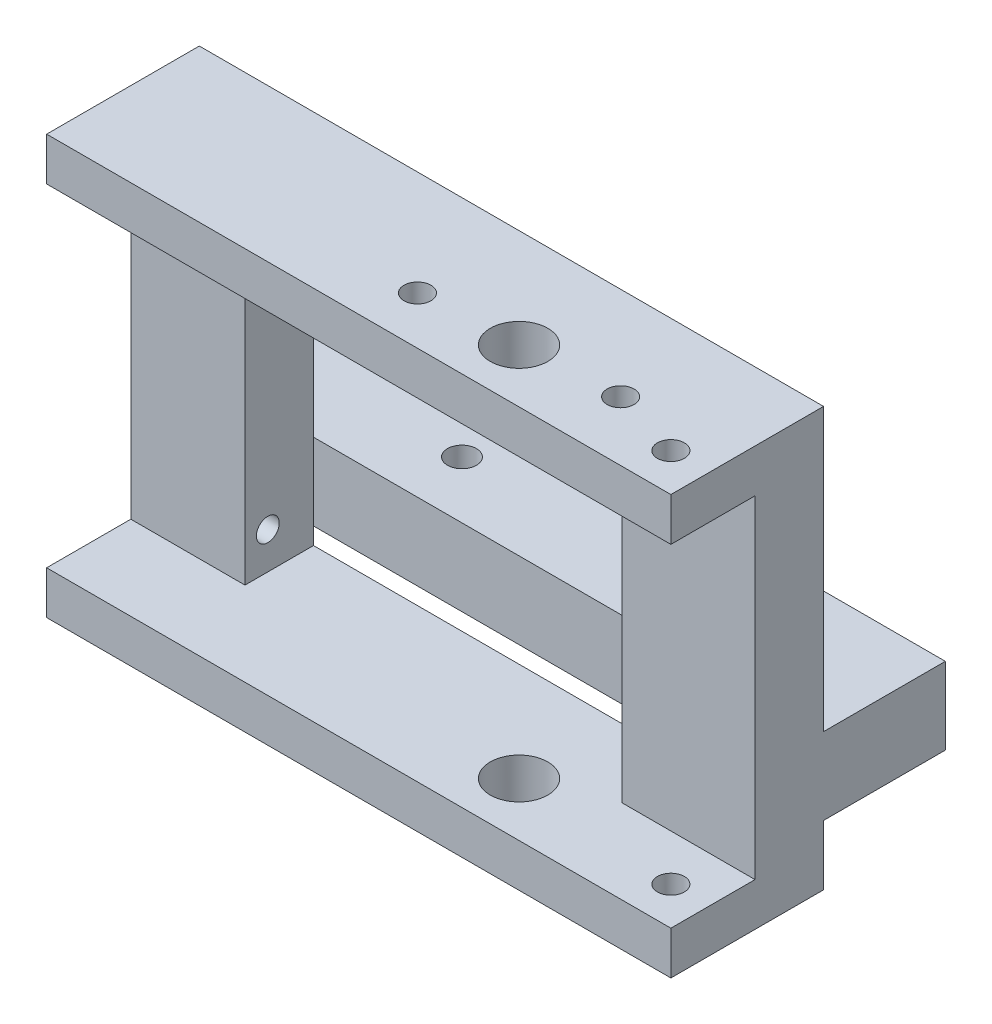
SolidWorks part; units mm, degrees
ref_plane "Front Plane" through (0, 0, 0) normal (0, 0, 1) x (1, 0, 0)
ref_plane "Top Plane" through (0, 0, 0) normal (0, 1, 0) x (1, 0, 0)
ref_plane "Right Plane" through (0, 0, 0) normal (1, 0, 0) x (0, 0, -1)
sketch "Sketch1" plane through (0, 0, 0) normal (0, 0, 1) x (1, 0, 0)
  line L1 (57.15, -34.925) -> (-57.15, -34.925)
  line L2 (57.15, -34.925) -> (57.15, 34.925)
  line L3 (57.15, 34.925) -> (-57.15, 34.925)
  line L4 (-57.15, -34.925) -> (-57.15, 34.925)
  line L5 (57.15, -34.925) -> (-57.15, 34.925) construction
  line L6 (57.15, 34.925) -> (-57.15, -34.925) construction
  point P0 (0, 0)
  dimension "D1" = 69.85
  dimension "D2" = 114.3
extrude "Boss-Extrude1" add sketch "Sketch1" along normal blind 57.15
sketch "Sketch2" plane through (0, 0, 57.15) normal (0, 0, 1) x (1, 0, 0)
  line L0 (-57.15, 34.925) -> (-57.15, -34.925) construction
  line L1 (57.15, -27.725) -> (-57.15, -27.725)
  line L2 (57.15, -27.725) -> (57.15, 27.725)
  line L3 (57.15, 27.725) -> (-57.15, 27.725)
  line L4 (-57.15, -27.725) -> (-57.15, 27.725)
  line L5 (57.15, -27.725) -> (-57.15, 27.725) construction
  line L6 (57.15, 27.725) -> (-57.15, -27.725) construction
  line L7 (57.15, 34.925) -> (-57.15, 34.925) construction
  point P0 (0, 0)
  dimension "D1" = 7.2
extrude "Cut-Extrude2" cut sketch "Sketch2" against normal blind 25.4
sketch "Sketch3" plane through (0, 0, 0) normal (0, 0, -1) x (-1, 0, 0)
  line L0 (-57.15, -34.925) -> (-57.15, 34.925) construction
  line L1 (57.15, 34.925) -> (-57.15, 34.925)
  line L2 (57.15, 34.925) -> (57.15, -12.065)
  line L3 (57.15, -12.065) -> (-57.15, -12.065)
  line L4 (-57.15, 34.925) -> (-57.15, -12.065)
  dimension "D1" = 46.99
extrude "Cut-Extrude3" cut sketch "Sketch3" against normal blind 20.32
sketch "Sketch5" plane through (0, -34.925, 0) normal (0, -1, 0) x (1, 0, 0)
  line L0 (-3.81, 10.79) -> (46.99, 10.79) construction
  line L1 (57.15, 20.32) -> (-57.15, 20.32) construction
  line L2 (57.15, 57.15) -> (57.15, 0) construction
  circle A0 centre (-3.81, 10.79) radius 2.415
  circle A1 centre (46.99, 10.79) radius 2.415
  dimension "D3" = 4.83
  dimension "D4" = 10.16
  dimension "D1" = 9.53
  dimension "D2" = 50.8
sketch "Sketch7" plane through (0, -34.925, 0) normal (0, -1, 0) x (1, 0, 0)
  line L0 (57.15, 57.15) -> (57.15, 0) construction
  line L2 (-57.15, 31.75) -> (57.15, 31.75) construction
  circle A0 centre (31.75, 36.83) radius 4.8
  dimension "D1" = 9.6
  dimension "D2" = 25.4
  dimension "D3" = 5.08
extrude "Cut-Extrude6" cut sketch "Sketch7" against normal up to surface (69.85 mm away) up to face at (0, 34.925, 38.735)
sketch "Sketch8" plane through (0, 34.925, 0) normal (0, 1, 0) x (1, 0, 0)
  line L0 (15.7798, -37.8068) -> (47.7202, -35.8532) construction
  line L1 (57.15, -31.75) -> (-57.15, -31.75) construction
  circle A0 centre (31.75, -36.83) radius 16 construction
  circle A1 centre (15.7798, -37.8068) radius 2.25
  circle A2 centre (47.7202, -35.8532) radius 2.25
  dimension "D1" = 32
  dimension "D2" = 4.5
  dimension "D3" = 3.5
sketch "Sketch9" plane through (0, 0, 31.75) normal (0, 0, 1) x (1, 0, 0)
  line L0 (57.15, 34.925) -> (-57.15, 34.925) construction
  line L5 (57.15, 27.725) -> (-57.15, 27.725) construction
  line L6 (-19.05, 27.725) -> (43.815, 27.725)
  line L7 (-19.05, 27.725) -> (-19.05, -27.725)
  line L8 (-19.05, -27.725) -> (43.815, -27.725)
  line L9 (43.815, 27.725) -> (43.815, -27.725)
  line L10 (-57.15, -27.725) -> (57.15, -27.725) construction
  line L11 (-57.15, 27.725) -> (-57.15, -27.725) construction
  line L12 (57.15, -27.725) -> (57.15, 27.725) construction
  line L13 (-57.15, -34.925) -> (-38.1, -34.925)
  line L14 (-57.15, -34.925) -> (-57.15, 34.925)
  line L15 (-57.15, 34.925) -> (-38.1, 34.925)
  line L16 (-38.1, -34.925) -> (-38.1, 34.925)
  line L17 (-57.15, -34.925) -> (-38.1, 34.925) construction
  line L18 (-57.15, 34.925) -> (-38.1, -34.925) construction
  line L19 (-57.15, -34.925) -> (57.15, -34.925) construction
  point P5 (-47.625, 0)
  dimension "D1" = 13.335
  dimension "25in" = 38.1
  dimension "D2" = 19.05
extrude "Cut-Extrude7" cut sketch "Sketch9" against normal through all both and the other way through all
extrude "Cut-Extrude8" cut sketch "Sketch8" against normal up to next
sketch "Sketch10" [suppressed] plane through (0, 0, 29.21) normal (0, 0, 1) x (1, 0, 0)
  line L1 (-30.607, -1.778) -> (-30.607, -6.604) construction
  circle A0 centre (-33.2489, -4.191) radius 2.286
  point P5 (-30.607, -4.191)
  dimension "D1" = 4.572
sketch "Sketch11" [suppressed] plane through (0, 0, 20.32) normal (0, 0, -1) x (-1, 0, 0)
  circle A0 centre (33.2489, -4.191) radius 2.286
  dimension "D1" = 4.572
extrude "Cut-Extrude9" [suppressed] cut sketch "Sketch11" against normal blind 3.81
sketch "Sketch12" plane through (-19.05, 0, 0) normal (1, 0, 0) x (0, 0, -1)
  line L0 (-31.75, -27.725) -> (-31.75, 27.725) construction
  line L1 (-27.94, -21.59) -> (-27.94, 21.59) construction
  line L2 (-20.32, 27.725) -> (-20.32, -12.065) construction
  circle A0 centre (-27.94, -21.59) radius 1.905
  circle A1 centre (-27.94, 21.59) radius 1.905
  point P0 (-31.75, 0)
  point P8 (-27.94, 0)
  dimension "D1" = 3.81
  dimension "D2" = 7.62
  dimension "D3" = 43.18
extrude "Cut-Extrude10" cut sketch "Sketch12" against normal up to surface (19.05 mm away) up to face at (-38.1, -2.413, 33.274)
sketch "Sketch13" plane through (0, 34.925, 0) normal (0, 1, 0) x (1, 0, 0)
  line L0 (-38.1, -45.7884) -> (57.15, -45.7884)
  line L2 (57.15, -57.15) -> (-38.1, -57.15) construction
  line L3 (47.7202, -35.8532) -> (15.7798, -37.8068) construction
  line L4 (-38.1, -45.7884) -> (-38.1, -57.15)
  line L5 (-38.1, -57.15) -> (57.15, -57.15)
  line L6 (-38.1, -20.32) -> (-38.1, -57.15) construction
  line L7 (57.15, -57.15) -> (57.15, -20.32) construction
  line L8 (57.15, -45.7884) -> (57.15, -57.15)
extrude "Cut-Extrude12" cut sketch "Sketch13" against normal through all
sketch "Sketch14" plane through (43.815, 0, 0) normal (-1, 0, 0) x (0, 0, 1)
  line L0 (0, -27.725) -> (31.75, -27.725) construction
  line L1 (20.32, -12.065) -> (0, -12.065)
  line L2 (20.32, -12.065) -> (20.32, -27.725)
  line L3 (20.32, -27.725) -> (0, -27.725)
  line L4 (0, -12.065) -> (0, -27.725)
extrude "Boss-Extrude2" add sketch "Sketch14" along normal up to next
sketch "Sketch16" plane through (0, 0, 31.75) normal (0, 0, 1) x (1, 0, 0)
  line L0 (43.815, -27.725) -> (43.815, 27.725) construction
  line L1 (57.15, -6.35) -> (43.815, -6.35)
  line L2 (57.15, -6.35) -> (57.15, 6.35)
  line L3 (57.15, 6.35) -> (43.815, 6.35)
  line L4 (43.815, -6.35) -> (43.815, 6.35)
  line L5 (57.15, -6.35) -> (43.815, 6.35) construction
  line L6 (57.15, 6.35) -> (43.815, -6.35) construction
  line L7 (57.15, 6.35) -> (57.15, -6.35) construction
  line L9 (57.15, -27.725) -> (57.15, 27.725) construction
  point P0 (50.4825, 0)
  point P7 (57.15, 0)
  dimension "D1" = 12.7
extrude "Boss-Extrude3" [suppressed] add sketch "Sketch16" along normal blind 12.7
sketch "Sketch17" [suppressed] plane through (0, 6.35, 0) normal (0, 1, 0) x (1, 0, 0)
  line L0 (49.375, -44.45) -> (57.15, -31.75)
  line L1 (57.15, -44.45) -> (57.15, -31.75) construction
  line L2 (57.15, -31.75) -> (43.815, -31.75) construction
  line L3 (57.15, -31.75) -> (57.15, -44.45)
  line L4 (57.15, -44.45) -> (49.375, -44.45)
  line L5 (57.15, -44.45) -> (43.815, -44.45) construction
extrude "Cut-Extrude14" [suppressed] cut sketch "Sketch17" against normal blind 12.7
fillet "Fillet4" [suppressed] radius 2.54
sketch "Sketch18" plane through (-38.1, 0, 0) normal (-1, 0, 0) x (0, 0, 1)
  line L0 (0, -34.925) -> (45.7884, -34.925) construction
  line L1 (20.32, -35.0627) -> (20.32, -24.9001)
  line L2 (20.32, -24.9001) -> (0, -24.9001)
  line L3 (0, -34.925) -> (0, -12.065) construction
  line L4 (0, -24.9001) -> (0, -34.925)
  line L5 (20.32, -34.925) -> (0, -34.925)
  point P0 (20.32, -34.925)
  point P1 (7.9478, 3.6724)
  line M3 (0, -34.925) -> (45.7884, -34.925)
  line M12 (0, -12.065) -> (0, -34.925)
sketch "Sketch19" plane through (-38.1, 0, 0) normal (-1, 0, 0) x (0, 0, 1)
  line L0 (20.32, -34.925) -> (0, -34.925)
sketch "Sketch20" plane through (-38.1, 0, 0) normal (-1, 0, 0) x (0, 0, 1)
  line L0 (0, -34.925) -> (45.7884, -34.925) construction
  line L1 (20.066, -34.925) -> (20.066, -24.765)
  line L2 (20.066, -24.765) -> (0, -24.765)
  line L3 (0, -34.925) -> (0, -12.065) construction
  line L4 (0, -24.765) -> (0, -34.925)
  line L5 (20.066, -34.925) -> (-0.1509, -34.925)
  point P0 (20.32, -34.925)
  dimension "D1" = 10.16
  dimension "D2" = 20.066
extrude "Cut-Extrude20" cut sketch "Sketch5" against normal through all contours A0 | A1
sketch "Sketch21" plane through (-38.1, 0, 0) normal (-1, 0, 0) x (0, 0, 1)
sketch "Sketch22" plane through (-38.1, 0, 0) normal (-1, 0, 0) x (0, 0, 1)
extrude "Cut-Extrude21" cut sketch "Sketch18" against normal through all contours L1 L2 M12 M3 region at (-38.1, -29.9125, 10.16)
sketch "Sketch23" plane through (0, -34.925, 0) normal (0, -1, 0) x (1, 0, 0)
  line L0 (57.15, 20.32) -> (57.15, 31.75)
  line L1 (57.15, 45.7884) -> (57.15, 20.32) construction
  circle A0 centre (52.07, 26.035) radius 2.413
  point P7 (57.15, 26.035)
  dimension "D2" = 4.826
  dimension "D1" = 11.43
  dimension "D3" = 5.08
sketch "Sketch24" plane through (0, 34.925, 0) normal (0, 1, 0) x (1, 0, 0)
  line L0 (47.7202, -35.8532) -> (15.7798, -37.8068)
  point P0 (47.7202, -35.8532)
  point P1 (15.7798, -37.8068)
sketch3d "3DSketch2"
  line L1 (47.7202, 34.925, 35.8532) -> (15.7798, 34.925, 37.8068) construction
fillet "Fillet5" [suppressed] radius 2.54
sketch "Sketch26" plane through (57.15, 0, 0) normal (1, 0, 0) x (0, 0, -1)
  line L28 (-45.7884, -34.925) -> (-20.32, -34.925)
  line L29 (-20.32, -34.925) -> (-20.32, -24.9001)
  line L30 (-20.32, -24.9001) -> (0, -24.9001)
  line L31 (0, -24.9001) -> (0, -12.065)
  line L32 (0, -12.065) -> (-20.32, -12.065)
  line L33 (-20.32, -12.065) -> (-20.32, 34.925)
  line L34 (-20.32, 34.925) -> (-45.7884, 34.925)
  line L35 (-45.7884, 34.925) -> (-45.7884, 27.725)
  line L36 (-45.7884, 27.725) -> (-31.75, 27.725)
  line L37 (-31.75, 27.725) -> (-31.75, -27.725)
  line L40 (-31.75, -27.725) -> (-45.7884, -27.725)
  line L41 (-45.7884, -27.725) -> (-45.7884, -34.925)
  line L42 (-45.7884, -34.925) -> (-20.32, -34.925)
  line L43 (-20.32, -34.925) -> (-20.32, -24.9001)
  line L44 (-20.32, -24.9001) -> (0, -24.9001)
  line L45 (0, -24.9001) -> (0, -12.065)
  line L46 (0, -12.065) -> (-20.32, -12.065)
  line L47 (-20.32, -12.065) -> (-20.32, 34.925)
  line L48 (-20.32, 34.925) -> (-45.7884, 34.925)
  line L49 (-45.7884, 34.925) -> (-45.7884, 27.725)
  line L50 (-45.7884, 27.725) -> (-31.75, 27.725)
  line L51 (-31.75, 27.725) -> (-31.75, -27.725)
  line L54 (-31.75, -27.725) -> (-45.7884, -27.725)
  line L55 (-45.7884, -27.725) -> (-45.7884, -34.925)
  dimension "D1" = 0
extrude "Boss-Extrude4" add sketch "Sketch26" along normal blind 8.89
sketch "Sketch31" plane through (0, 34.925, 0) normal (0, 1, 0) x (1, 0, 0)
  line L0 (66.04, -45.7884) -> (-38.1, -45.7884) construction
  line L1 (66.04, -20.32) -> (66.04, -45.7884) construction
  point P0 (59.69, -39.4384)
  dimension "D1" = 6.35
  dimension "D2" = 6.35
hole_wizard "#8 Clearance Hole1" positions "Sketch31" profile "Sketch30" hole size "#8" standard "ANSI Inch" end condition through all
sketch "Sketch30" plane through (59.69, 34.925, 39.4384) normal (1, 0, 0) x (0, 0, 1)
  line L0 (0, 0) -> (0, 69.85)
  line L1 (0, 69.85) -> (2.2479, 69.85)
  line L2 (2.2479, 69.85) -> (2.2479, 0)
  line L5 (2.2479, 0) -> (0, 0)
  line L11 (0, -6.35) -> (0, 107.95) construction
  dimension "Thru Hole Dia." = 4.4958
  dimension "Thru Hole Depth" = 69.85
